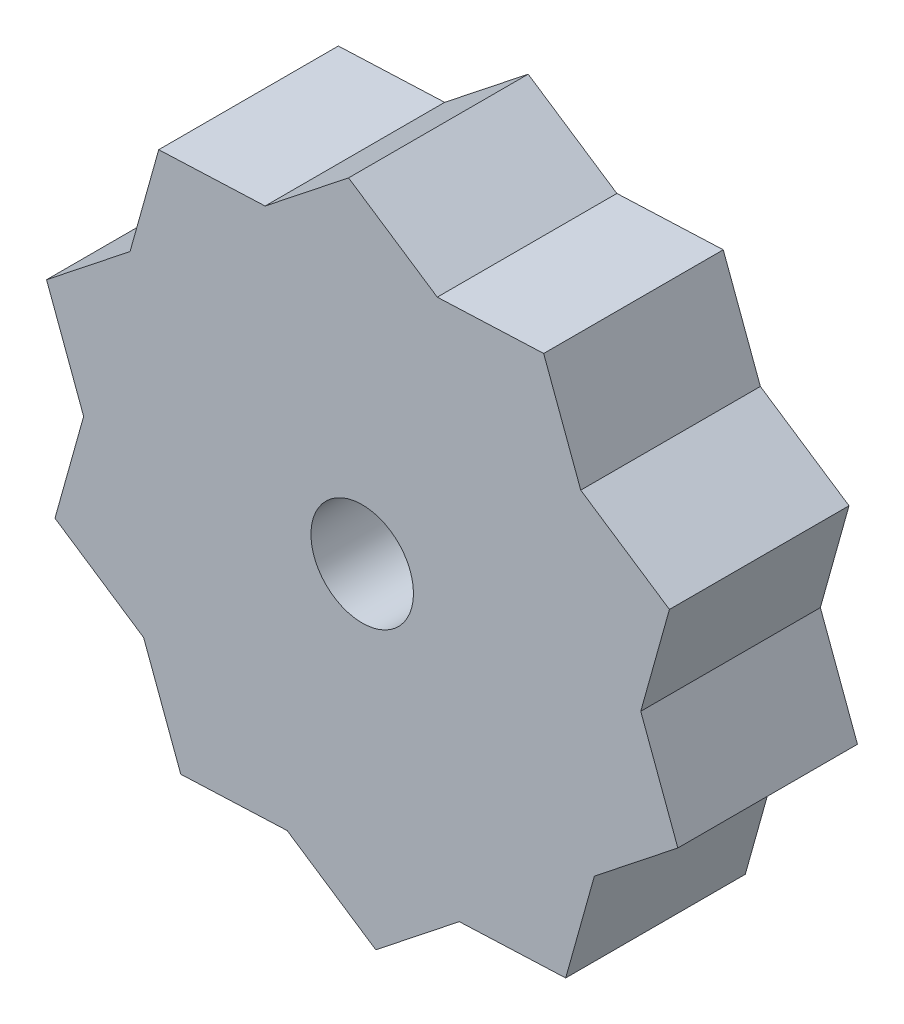
SolidWorks part; units mm, degrees
ref_plane "Front Plane" through (0, 0, 0) normal (0, 0, 1) x (1, 0, 0)
ref_plane "Top Plane" through (0, 0, 0) normal (0, 1, 0) x (1, 0, 0)
ref_plane "Right Plane" through (0, 0, 0) normal (1, 0, 0) x (0, 0, -1)
sketch "Sketch2" plane through (0, 0, 0) normal (0, 0, 1) x (1, 0, 0)
  line L0 (5.1329, 7.7198) -> (-5.7558, 7.2672)
  line L1 (-8.9281, 2.4961) -> (-5.1329, -7.7198)
  line L2 (-5.1329, -7.7198) -> (5.7558, -7.2672)
  line L3 (5.7558, -7.2672) -> (8.6902, 3.2284)
  line L4 (8.6902, 3.2284) -> (-0.385, 9.2625)
  line L5 (-5.7558, 7.2672) -> (-8.6902, -3.2284)
  line L6 (-0.385, 9.2625) -> (-8.9281, 2.4961)
  line L8 (-8.6902, -3.2284) -> (0, 0)
  line L9 (-8.6902, -3.2284) -> (0.385, -9.2625)
  line L10 (0.385, -9.2625) -> (8.9281, -2.4961)
  line L11 (8.9281, -2.4961) -> (5.1329, 7.7198)
  circle A0 centre (0, 0) radius 1.45
  circle A1 centre (0, 0) radius 7.5 construction
  circle A2 centre (0, 0) radius 7.5 construction
  dimension "D1" = 2.9
  dimension "D2" = 15
  dimension "D3" = 15
  dimension "D4" = 90
extrude "Boss-Extrude1" add sketch "Sketch2" along normal blind 5.08 contours L9 L10 L2 | L10 L2 L3 | L11 L3 L4 | L10 L11 L3 | L4 L11 L0 | L4 L6 L0 | L6 L0 L5 | L5 L6 L1 | L5 L8 L1 | L8 L9 L1 | A0 L1 L9 L2 L10 L3 L11 L4 L0 L6 L5 | L1 L2 L3 L4 L6 region at (4.4794, 6.7369, 0) region at (4.0314, 6.0632, 0) region at (-0.336, 8.0832, 0) region at (7.5837, 2.8174, 0) region at (-5.023, 6.342, 0) region at (7.7914, -2.1783, 0) region at (-7.7914, 2.1783, 0) region at (5.023, -6.342, 0) region at (-7.8666, -2.0559, 0) region at (0.336, -8.0832, 0) region at (-7.3009, -3.5788, 0)
extrude "Cut-Extrude1" cut sketch "Sketch2<3>" along normal through all contours A0
sketch "Sketch2<3>" plane through (0, 0, 0) normal (0, 0, 1) x (1, 0, 0) same geometry as "Sketch2"
